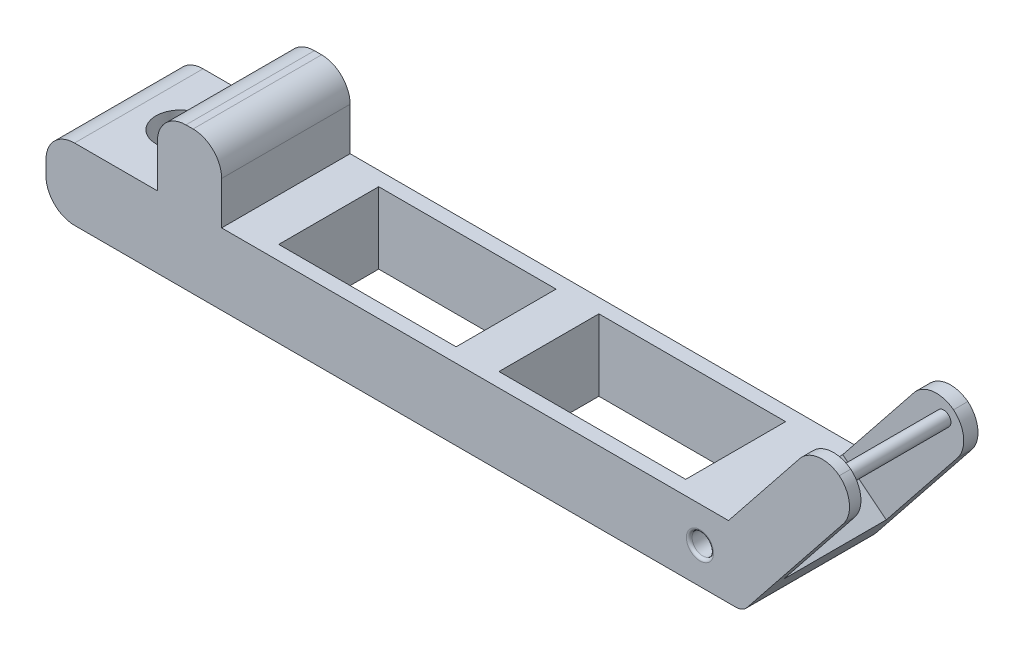
SolidWorks part; units mm, degrees
ref_plane "Front Plane" through (0, 0, 0) normal (0, 0, 1) x (1, 0, 0)
ref_plane "Top Plane" through (0, 0, 0) normal (0, 1, 0) x (1, 0, 0)
ref_plane "Right Plane" through (0, 0, 0) normal (1, 0, 0) x (0, 0, -1)
sketch "Szkic1" plane through (0, 0, 0) normal (0, 0, 1) x (1, 0, 0)
  line L6 (-27646.5587, -28.9023) -> (-27646.5587, -33.9023)
  line L7 (-27646.5587, -33.9023) -> (-27597.7587, -33.9023)
  line L8 (-27597.7587, -33.9023) -> (-27589.4735, -23.5176)
  line L9 (-27589.4735, -23.5176) -> (-27592.5221, -21.0854)
  line L10 (-27592.5221, -21.0854) -> (-27598.7587, -28.9023)
  line L11 (-27598.7587, -28.9023) -> (-27634.2587, -28.9023)
  line L12 (-27638.7587, -28.9023) -> (-27638.7587, -23.9023)
  line L13 (-27638.7587, -23.9023) -> (-27634.2587, -23.9023)
  line L14 (-27634.2587, -23.9023) -> (-27634.2587, -28.9023)
  line L15 (-27638.7587, -28.9023) -> (-27646.5587, -28.9023)
  line L16 (-27600.7587, -28.9023) -> (-27600.7587, -33.9023) construction
  circle A0 centre (-27600.7587, -31.4023) radius 0.75
  point P12 (-27600.7587, -31.4023)
  dimension "D9" = 1.5
  dimension "D1" = 3.9
  dimension "D2" = 47.8
  dimension "D3" = 10
  dimension "D4" = 5
  dimension "D5" = 48.8
  dimension "D6" = 4.5
  dimension "D7" = 5
  dimension "D8" = 7.8
  dimension "D10" = 2
extrude "Dodanie-wyciągnięcie1" add sketch "Szkic1" along normal blind 9
fillet "Zaokrąglenie1" radius 2 4 edges at (-27646.5587, -33.9023, 4.5) (-27634.2587, -23.9023, 4.5) (-27638.7587, -23.9023, 4.5) (-27646.5587, -28.9023, 4.5)
fillet "Zaokrąglenie3" radius 1 1 edges at (-27597.7587, -33.9023, 4.5)
ref_plane "Płaszczyzna1" through (0, -28.9023, 0) normal (0, 1, 0) x (1, 0, 0)
sketch "Szkic2" plane through (0, -28.9023, 0) normal (0, 1, 0) x (1, 0, 0)
  line L0 (-27641.6587, 0) -> (-27641.6587, -9) construction
  line L1 (-27638.7587, 0) -> (-27644.5587, 0) construction
  line L2 (-27638.7587, -9) -> (-27644.5587, -9) construction
  circle A0 centre (-27641.6587, -4.5) radius 1.7
  point P6 (-27641.6587, -4.5)
  dimension "D1" = 3.4
extrude "Wytnij-wyciągnięcie1" cut sketch "Szkic2" against normal through all
ref_plane "Płaszczyzna2" through (0, -28.9023, 0) normal (0, 1, 0) x (1, 0, 0)
sketch "Szkic3" plane through (0, -28.9023, 0) normal (0, 1, 0) x (1, 0, 0)
  line L0 (-27634.2587, -4.5) -> (-27598.7587, -4.5) construction
  line L1 (-27634.2587, -9) -> (-27634.2587, 0) construction
  line L2 (-27598.7587, -9) -> (-27598.7587, 0) construction
  line L3 (-27598.7587, -9) -> (-27634.2587, -9) construction
  line L4 (-27602.7587, -8) -> (-27615.8361, -8)
  line L5 (-27602.7587, -8) -> (-27602.7587, -1)
  line L6 (-27602.7587, -1) -> (-27615.8361, -1)
  line L7 (-27615.8361, -8) -> (-27615.8361, -1)
  line L8 (-27602.7587, -8) -> (-27615.8361, -1) construction
  line L9 (-27602.7587, -1) -> (-27615.8361, -8) construction
  line L10 (-27631.2587, -1) -> (-27618.8361, -1)
  line L11 (-27631.2587, -1) -> (-27631.2587, -8)
  line L12 (-27631.2587, -8) -> (-27618.8361, -8)
  line L13 (-27618.8361, -1) -> (-27618.8361, -8)
  line L14 (-27631.2587, -1) -> (-27618.8361, -8) construction
  line L15 (-27631.2587, -8) -> (-27618.8361, -1) construction
  point P6 (-27609.2974, -4.5)
  point P11 (-27625.0474, -4.5)
  dimension "D1" = 3
  dimension "D2" = 4
  dimension "D3" = 3
  dimension "D4" = 1
extrude "Wytnij-wyciągnięcie2" cut sketch "Szkic3" against normal through all
ref_plane "Płaszczyzna3" through (-16850.0467, 13443.5022, 0) normal (-0.7817, 0.6237, 0) x (0, 0, 1)
sketch "Szkic4" plane through (-16850.0467, 13443.5022, 0) normal (-0.7817, 0.6237, 0) x (0, 0, 1)
  line L0 (9, -17234.8628) -> (0, -17234.8628) construction
  line L1 (1, -17234.8628) -> (8.2, -17234.8628)
  line L2 (1, -17234.8628) -> (1, -17222.0924)
  line L3 (1, -17222.0924) -> (8.2, -17222.0924)
  line L4 (8.2, -17234.8628) -> (8.2, -17222.0924)
  line L5 (0, -17224.8628) -> (0, -17234.8628) construction
  dimension "D1" = 7.2
  dimension "D2" = 1
extrude "Wytnij-wyciągnięcie3" cut sketch "Szkic4" against normal through all
ref_plane "Płaszczyzna4" through (0, 0, 1) normal (0, 0, 1) x (1, 0, 0)
sketch "Szkic5" plane through (0, 0, 1) normal (0, 0, 1) x (1, 0, 0)
  line L0 (-27590.9978, -22.3015) -> (-27597.2344, -30.1185) construction
  line L1 (-27592.5221, -21.0854) -> (-27589.4735, -23.5176) construction
  line L2 (-27595.7101, -31.3346) -> (-27598.7587, -28.9023) construction
  circle A0 centre (-27592.3166, -23.9544) radius 0.5
  dimension "D1" = 1
extrude "Dodanie-wyciągnięcie2" [suppressed] add sketch "Szkic5" along normal up to next
fillet "Zaokrąglenie4" radius 2 4 edges at (-27589.4735, -23.5176, 0.5) (-27592.5221, -21.0854, 0.5) (-27589.4735, -23.5176, 8.6) (-27592.5221, -21.0854, 8.6)
fillet "Zaokrąglenie5" radius 1 1 edges at (-27643.3587, -33.9023, 4.5)
ref_axis "Oś1" through (-27641.6587, -32.9023, 4.5) along (0, 1, 0)
ref_point "Punkt1"
ref_point "Punkt2"
fillet "Zaokrąglenie7" radius 0.2 2 edges at (-27600.0087, -31.4023, 9) (-27600.0087, -31.4023, 0)
ref_plane "Płaszczyzna Dolnia" through (0, -33.9023, 0) normal (0, -1, 0) x (-1, 0, 0)
sketch "Szkic6" plane through (0, 0, 1) normal (0, 0, 1) x (1, 0, 0)
  line L0 (-27595.4545, -24.7608) -> (-27592.4059, -27.1931)
  line L1 (-27590.7208, -25.081) -> (-27595.7101, -31.3346) construction
  line L2 (-16849.7037, 13443.9321) -> (-16850.3897, 13443.0723) construction
  line L3 (-27593.9302, -25.977) -> (-27590.9982, -22.302)
  circle A0 centre (-27591.6842, -23.1619) radius 0.5
  arc A1 (-27590.7208, -25.081) -> (-27590.9982, -22.302) centre (-27592.2842, -23.8337) ccw construction
  dimension "D1" = 1
  dimension "D2" = 1.1
extrude "Dodanie-wyciągnięcie3" add sketch "Szkic6" along normal up to surface (7.2 mm away) contours L3 A0 | L3 A0 region at (-27591.8501, -23.0295, 1) region at (-27591.5184, -23.2942, 1) up to face at (-27593.8925, -25.9297, 8.2)
